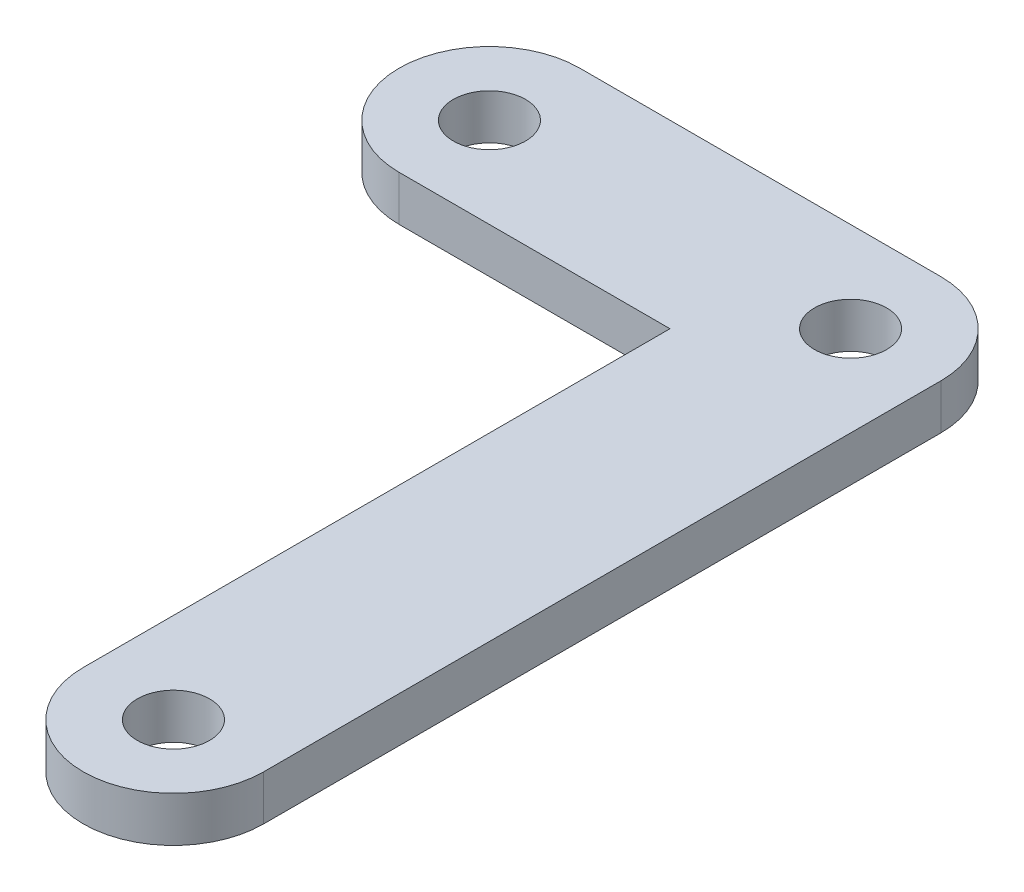
SolidWorks part; units mm, degrees
ref_plane "Front Plane" through (0, 0, 0) normal (0, 0, 1) x (1, 0, 0)
ref_plane "Top Plane" through (0, 0, 0) normal (0, 1, 0) x (1, 0, 0)
ref_plane "Right Plane" through (0, 0, 0) normal (1, 0, 0) x (0, 0, -1)
ref_axis "X" through (-88.99, 0, 0) along (1, 0, 0)
ref_axis "Y" through (0, 55, 0) along (0, -1, 0)
ref_axis "Z" through (0, 0, -88.99) along (0, 0, 1)
sketch "Sketch1" plane through (0, 0, 0) normal (0, 1, 0) x (1, 0, 0)
  line L0 (0, 0) -> (0, 75) construction
  line L1 (0, 75) -> (-40, 75) construction
  line L2 (-40, 85) -> (0, 85)
  line L3 (-40, 65) -> (-10, 65)
  line L4 (-10, 0) -> (-10, 65)
  line L5 (10, 75) -> (10, 0)
  circle A0 centre (0, 0) radius 10 construction
  circle A1 centre (0, 75) radius 10 construction
  circle A2 centre (-40, 75) radius 10 construction
  arc A3 (-40, 85) -> (-40, 65) centre (-40, 75) ccw
  arc A4 (0, 85) -> (10, 75) centre (0, 75) cw
  arc A5 (-10, 0) -> (10, 0) centre (0, 0) ccw
  dimension "D1" = 20
  dimension "D2" = 75
  dimension "D4" = 20
  dimension "D5" = 20
  dimension "D3" = 40
extrude "Boss-Extrude1" add sketch "Sketch1" along normal blind 5
sketch "Sketch2" plane through (0, 0, 0) normal (0, -1, 0) x (1, 0, 0)
  line L0 (-40, -75) -> (0, -75) construction
  line L1 (0, -75) -> (0, 0) construction
  circle A0 centre (0, 0) radius 4
  circle A1 centre (-40, -75) radius 4
  circle A2 centre (0, -75) radius 4
  dimension "D1" = 8
  dimension "D2" = 8
  dimension "D3" = 8
extrude "Cut-Extrude1" cut sketch "Sketch2" against normal blind 5
